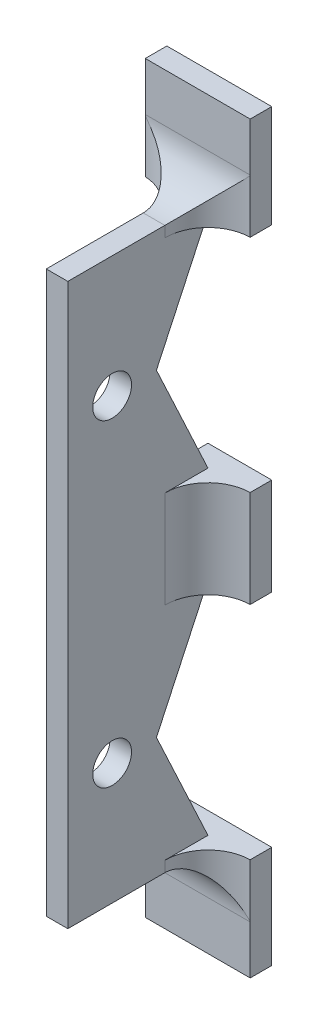
SolidWorks part; units mm, degrees
ref_plane "Front Plane" through (0, 0, 0) normal (0, 0, 1) x (1, 0, 0)
ref_plane "Top Plane" through (0, 0, 0) normal (0, 1, 0) x (1, 0, 0)
ref_plane "Right Plane" through (0, 0, 0) normal (1, 0, 0) x (0, 0, -1)
sketch "Sketch2" plane through (0, 0, 11.2114) normal (0, 0, 1) x (1, 0, 0)
  line L2 (-0.6907, -47.5128) -> (5.2255, -47.5128)
  line L3 (-0.6907, -47.5128) -> (-0.6907, -38.5128)
  line L4 (-3.8907, -18.2128) -> (-3.8907, -67.8128)
  line L5 (-3.8907, -67.8128) -> (-0.8907, -67.8128)
  line L6 (-0.8907, -67.8128) -> (-0.8907, -18.2128)
  line L7 (-0.8907, -18.2128) -> (-3.8907, -18.2128)
  line L8 (-3.8907, -18.2128) -> (-3.8907, -67.8128) construction
  line L9 (-3.8907, -67.8128) -> (-0.8907, -67.8128) construction
  line L10 (-0.8907, -67.8128) -> (-0.8907, -18.2128) construction
  line L11 (-0.8907, -18.2128) -> (-3.8907, -18.2128) construction
  line L12 (-0.6907, -38.5128) -> (5.2255, -38.5128)
  line L13 (5.2255, -47.5128) -> (5.2255, -38.5128)
  line L14 (-4.5065, -77.5128) -> (5.2255, -77.5128)
  line L16 (-4.5065, -68.0128) -> (5.2255, -68.0128)
  line L17 (5.2255, -77.5128) -> (5.2255, -68.0128)
  line L19 (-4.5065, -8.5128) -> (-4.5065, -18.0128)
  line L20 (-10.507, -67.8128) -> (-5.0065, -67.8128)
  line L21 (-5.0065, -67.8128) -> (-5.0065, -78.0128)
  line L22 (-5.0065, -78.0128) -> (5.7255, -78.0128)
  line L23 (5.7255, -78.0128) -> (5.7255, -68.0128)
  line L24 (5.7255, -68.0128) -> (0.1095, -68.0128)
  line L25 (0.1095, -68.0128) -> (0.1095, -48.0128)
  line L26 (0.1095, -48.0128) -> (5.7255, -48.0128)
  line L27 (5.7255, -48.0128) -> (5.7255, -38.0128)
  line L28 (5.7255, -38.0128) -> (0.1095, -38.0128)
  line L29 (0.1095, -38.0128) -> (0.1095, -18.0128)
  line L30 (0.1095, -18.0128) -> (5.7255, -18.0128)
  line L31 (5.7255, -18.0128) -> (5.7255, -8.0128)
  line L32 (5.7255, -8.0128) -> (-5.0065, -8.0128)
  line L33 (-5.0065, -8.0128) -> (-5.0065, -18.2128)
  line L34 (-5.0065, -18.2128) -> (-10.507, -18.2128)
  line L35 (-10.507, -18.2128) -> (-10.507, -37.8128)
  line L36 (-10.507, -37.8128) -> (-5.0065, -37.8128)
  line L37 (-5.0065, -37.8128) -> (-5.0065, -48.2128)
  line L38 (-5.0065, -48.2128) -> (-10.507, -48.2128)
  line L39 (-10.507, -48.2128) -> (-10.507, -67.8128)
  line L40 (-10.507, -67.8128) -> (-5.0065, -67.8128) construction
  line L43 (5.7255, -78.0128) -> (5.7255, -68.0128) construction
  line L44 (5.7255, -68.0128) -> (0.1095, -68.0128) construction
  line L45 (0.1095, -68.0128) -> (0.1095, -48.0128) construction
  line L46 (0.1095, -48.0128) -> (5.7255, -48.0128) construction
  line L47 (5.7255, -48.0128) -> (5.7255, -38.0128) construction
  line L48 (5.7255, -38.0128) -> (0.1095, -38.0128) construction
  line L49 (0.1095, -38.0128) -> (0.1095, -18.0128) construction
  line L50 (0.1095, -18.0128) -> (5.7255, -18.0128) construction
  line L51 (5.7255, -18.0128) -> (5.7255, -8.0128) construction
  line L52 (5.7255, -8.0128) -> (-5.0065, -8.0128) construction
  line L53 (-5.0065, -8.0128) -> (-5.0065, -18.2128) construction
  line L54 (-5.0065, -18.2128) -> (-10.507, -18.2128) construction
  line L55 (-10.507, -18.2128) -> (-10.507, -37.8128) construction
  line L56 (-10.507, -37.8128) -> (-5.0065, -37.8128) construction
  line L57 (-5.0065, -37.8128) -> (-5.0065, -48.2128) construction
  line L58 (-5.0065, -48.2128) -> (-10.507, -48.2128) construction
  line L59 (-10.507, -48.2128) -> (-10.507, -67.8128) construction
  line L61 (5.2255, -43.0128) -> (-0.6907, -43.0128) construction
  line L62 (-4.5065, -77.5128) -> (-4.5065, -68.0128)
  line L63 (-5.0065, -78.0128) -> (5.7255, -78.0128) construction
  line L64 (-5.0065, -78.0128) -> (5.7255, -78.0128) construction
  line L65 (-5.0065, -67.8128) -> (-5.0065, -78.0128) construction
  line L66 (-5.0065, -67.8128) -> (-5.0065, -78.0128) construction
  line L67 (-4.5065, -18.0128) -> (5.2255, -18.0128)
  line L68 (5.2255, -8.5128) -> (5.2255, -18.0128)
  line L69 (-4.5065, -8.5128) -> (5.2255, -8.5128)
  dimension "D3" = 0.5
  dimension "D4" = 0.5
  dimension "D5" = 0.5
  dimension "D6" = 0.2
  dimension "D7" = 0.5
  dimension "D9" = 0.2
  dimension "D8" = 0.5
  dimension "D10" = 0.5
  dimension "D1" = 0
  dimension "D2" = 0
extrude "Boss-Extrude1" add sketch "Sketch2" along normal blind 2
sketch "Sketch3" plane through (0, 0, 13.2114) normal (0, 0, 1) x (1, 0, 0)
  line L0 (-0.6907, -38.5128) -> (-0.6907, -47.5128) construction
  line L1 (-0.6907, -38.5128) -> (-0.6907, -47.5128)
  line L2 (-0.6907, -43.0128) -> (5.2255, -43.0128) construction
  line L3 (-0.6907, -17.0128) -> (1.3093, -17.0128)
  line L4 (-0.6907, -17.0128) -> (-0.6907, -69.0128)
  line L5 (-0.6907, -69.0128) -> (1.3093, -69.0128)
  line L6 (1.3093, -17.0128) -> (1.3093, -69.0128)
  line L7 (5.2255, -47.5128) -> (5.2255, -38.5128) construction
  line L8 (5.2255, -43.0128) -> (1.3093, -43.0128) construction
  line L9 (5.2255, -68.0128) -> (-4.5065, -68.0128) construction
  point P13 (0.3595, -68.0128)
  line M10 (5.2255, -68.0128) -> (-4.5065, -68.0128)
  dimension "D1" = 2
  dimension "D2" = 1
extrude "Boss-Extrude2" add sketch "Sketch3" along normal blind 13 contours L6 L3 L4 L1 M10 | L6 L4 L5 M10 region at (0.3093, -42.5128, 13.2114) region at (0.3093, -68.5128, 13.2114)
fillet "Fillet1" radius 4 7 edges at (-0.6907, -17.5128, 13.2114) (0.3093, -17.0128, 13.2114) (1.3093, -17.5128, 13.2114) (1.3093, -43.0128, 13.2114) (-0.6907, -68.5128, 13.2114) (1.3093, -68.5128, 13.2114) (0.3093, -69.0128, 13.2114)
sketch "Sketch6" plane through (1.3093, 0, 0) normal (1, 0, 0) x (0, 0, -1)
  line L0 (-13.2114, -68.0128) -> (-17.9911, -57.7628)
  line L1 (-17.9911, -57.7628) -> (-13.2114, -47.5128)
  line L2 (-17.2106, -43.0128) -> (-26.2114, -43.0128) construction
  line L3 (-13.2114, -57.7628) -> (-17.9911, -57.7628) construction
  line L4 (-13.2114, -68.0128) -> (-13.2114, -57.7628) construction
  line L5 (-13.2114, -47.5128) -> (-13.2114, -68.0128) construction
  line L6 (-17.9911, -28.2628) -> (-13.2114, -38.5128)
  line L7 (-13.2114, -18.0128) -> (-17.9911, -28.2628)
  line L8 (-26.2114, -17.0128) -> (-26.2114, -69.0128) construction
  line L9 (-26.2114, -69.0128) -> (-17.2114, -69.0128) construction
  line L10 (-26.2114, -17.0128) -> (-17.2114, -17.0128) construction
  line L11 (-17.2106, -18.0128) -> (-17.2106, -17.0128) construction
  line L12 (-17.2106, -18.0128) -> (-13.2114, -18.0128) construction
  line L13 (-17.2106, -69.0128) -> (-17.2106, -68.0128) construction
  line L14 (-17.2106, -47.5128) -> (-17.2106, -38.5128) construction
  line L15 (-13.2114, -38.5128) -> (-17.2106, -38.5128) construction
  line L17 (-13.2114, -38.5128) -> (-13.2114, -18.0128)
  line L26 (-13.2114, -68.0128) -> (-13.2114, -47.5128)
  line L34 (-13.2114, -18.0128) -> (-17.2106, -18.0128) construction
  line L35 (-17.2106, -18.0128) -> (-17.2106, -17.0128) construction
  line L36 (-17.2106, -17.0128) -> (-26.2114, -17.0128) construction
  line L37 (-26.2114, -17.0128) -> (-26.2114, -69.0128) construction
  line L38 (-26.2114, -69.0128) -> (-17.2106, -69.0128) construction
  line L39 (-17.2106, -69.0128) -> (-17.2106, -68.0128) construction
  line L40 (-17.2106, -68.0128) -> (-13.2114, -68.0128) construction
  line L44 (-13.2114, -47.5128) -> (-17.2106, -47.5128) construction
  line L45 (-17.2106, -47.5128) -> (-17.2106, -38.5128) construction
  line L46 (-17.2106, -38.5128) -> (-13.2114, -38.5128) construction
  point P0 (-13.2114, -57.7628)
  point P14 (0, 0)
  line M39 (-13.2114, -38.5128) -> (-13.2114, -18.0128)
  line M40 (-13.2114, -68.0128) -> (-13.2114, -47.5128)
  dimension "D2" = 25
extrude "Cut-Extrude1" cut sketch "Sketch6" against normal through all contours L7 L6 M39 | L1 L0 M40 region at (1.3093, -57.7628, 14.8047) region at (1.3093, -28.2628, 14.8047)
sketch "Sketch7" plane through (1.3093, 0, 0) normal (1, 0, 0) x (0, 0, -1)
  line L0 (-17.2106, -43.0128) -> (-26.2114, -43.0128) construction
  line L1 (-17.2106, -47.5128) -> (-17.2106, -38.5128) construction
  line L2 (-26.2114, -17.0128) -> (-26.2114, -69.0128) construction
  line L3 (-17.9911, -57.7628) -> (-26.2114, -57.7628) construction
  point P12 (-22.1013, -57.7628)
  point P15 (-22.1013, -28.2628)
hole_wizard "M3 Clearance Hole2" positions "Sketch7" profile "Sketch8" hole size "M3" standard "ANSI Metric" end condition through all
sketch "Sketch8" plane through (1.3093, -28.2628, 22.1013) normal (0, 1, 0) x (0, 0, -1)
  line L0 (0, 0) -> (0, 6.2626)
  line L1 (0, 6.2626) -> (1.8, 6.2626)
  line L2 (1.8, 6.2626) -> (1.8, 0)
  line L5 (1.8, 0) -> (0, 0)
  line L11 (0, -6.35) -> (0, 107.95) construction
  dimension "Thru Hole Dia." = 3.6
  dimension "Thru Hole Depth" = 6.2626
equation "\"D5@Sketch2\"=\"D4@Sketch2\""
equation "\"D7@Sketch2\"=\"D3@Sketch2\""
equation "\"D9@Sketch2\"=\"D6@Sketch2\""
equation "\"D8@Sketch2\"=\"D7@Sketch2\""
equation "\"D10@Sketch2\"=\"D7@Sketch2\""
